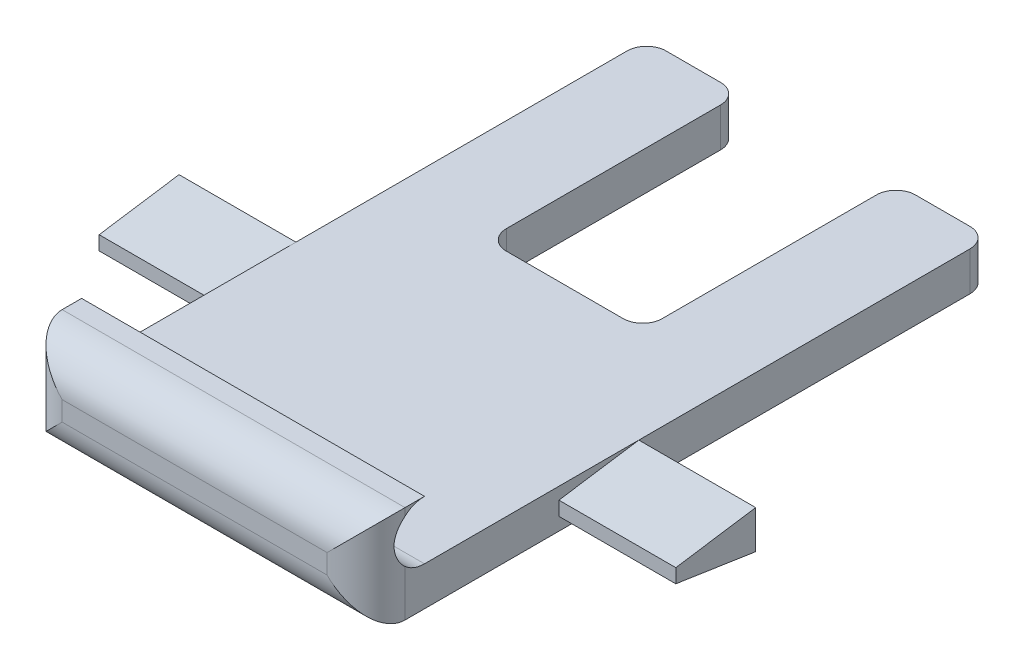
SolidWorks part; units mm, degrees
ref_plane "Front Plane" through (0, 0, 0) normal (0, 0, 1) x (1, 0, 0)
ref_plane "Top Plane" through (0, 0, 0) normal (0, 1, 0) x (1, 0, 0)
ref_plane "Right Plane" through (0, 0, 0) normal (1, 0, 0) x (0, 0, -1)
sketch "Sketch1" plane through (0, 0, 0) normal (0, 1, 0) x (1, 0, 0)
  line L1 (0, 0) -> (88, 0)
  line L2 (0, 0) -> (0, 160)
  line L3 (0, 160) -> (88, 160)
  line L4 (88, 0) -> (88, 160)
  dimension "D1" = 88
  dimension "D2" = 160
extrude "Boss-Extrude1" add sketch "Sketch1" along normal blind 10
sketch "Sketch2" plane through (0, 10, 0) normal (0, 1, 0) x (1, 0, 0)
  line L0 (88, 0) -> (88, 160) construction
  line L1 (0, 0) -> (88, 0)
  line L2 (0, 0) -> (0, 15)
  line L3 (0, 15) -> (88, 15)
  line L4 (88, 0) -> (88, 15)
  dimension "D1" = 15
extrude "Boss-Extrude2" add sketch "Sketch2" along normal blind 15
sketch "Sketch3" plane through (88, 0, 0) normal (1, 0, 0) x (0, 0, -1)
  line L0 (15, 25) -> (15, 10) construction
  circle A0 centre (15, 17.5) radius 7.5
  dimension "D1" = 15
extrude "Cut-Extrude1" cut sketch "Sketch3" against normal up to surface (88 mm away) up to face at (0, 11.6667, -58.3333)
fillet "Fillet1" radius 10 4 edges at (0, 12.5, 0) (44, 25, 0) (88, 12.5, 0) (44, 0, 0)
sketch "Sketch4" plane through (0, 10, 0) normal (0, 1, 0) x (1, 0, 0)
  line L0 (88, 160) -> (0, 160) construction
  line L1 (24, 160) -> (64, 160)
  line L2 (24, 160) -> (24, 95)
  line L3 (24, 95) -> (64, 95)
  line L4 (64, 160) -> (64, 95)
  line L6 (88, 15) -> (88, 160) construction
  line L7 (64, 95) -> (88, 95) construction
  line L8 (24, 95) -> (0, 95) construction
  line L9 (0, 160) -> (0, 15) construction
  dimension "D1" = 40
  dimension "D2" = 65
extrude "Cut-Extrude2" cut sketch "Sketch4" against normal up to surface (10 mm away) contours L2 L1 L4 L3 up to face at (44, 0, -85)
fillet "Fillet2" radius 5 4 edges at (64, 5, -160) (24, 5, -160) (24, 5, -95) (64, 5, -95)
fillet "Fillet3" radius 5 2 edges at (88, 5, -160) (0, 5, -160)
sketch "Sketch5" plane through (0, 0, 0) normal (-1, 0, 0) x (0, 0, 1)
  line L0 (-155, 10) -> (-15, 10) construction
  line L2 (-70, 10) -> (-70, 0.2)
  line L6 (-70, 10) -> (-49.5, 6.9)
  line L7 (-49.5, 6.9) -> (-49.5, 3.3)
  line L8 (-49.5, 3.3) -> (-70, 0.2)
  line L9 (-70, 5.1) -> (-46.86, 5.1) construction
  line L10 (-10, 0) -> (-10, 11.9098) construction
  point P8 (-69.5, 3)
  point P11 (0, 0)
  dimension "D1" = 9.8
  dimension "D2" = 1.8
  dimension "D3" = 1.8
  dimension "D4" = 20.5
  dimension "D5" = 60
extrude "Boss-Extrude4" add sketch "Sketch5" along normal blind 30
ref_plane "Plane2" through (44, 0, 0) normal (1, 0, 0) x (0, 0, -1)
mirror "Mirror1" about plane through (44, 0, 0) normal (1, 0, 0) of "Boss-Extrude4"
